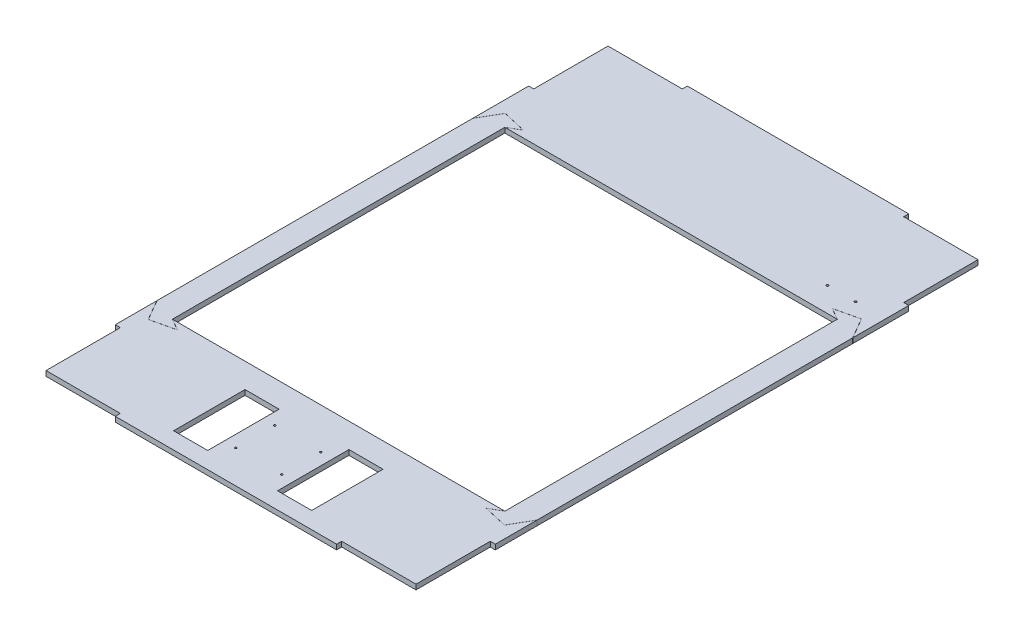
SolidWorks part; units mm, degrees
ref_plane "Front Plane" through (0, 0, 0) normal (0, 0, 1) x (1, 0, 0)
ref_plane "Top Plane" through (0, 0, 0) normal (0, 1, 0) x (1, 0, 0)
ref_plane "Right Plane" through (0, 0, 0) normal (1, 0, 0) x (0, 0, -1)
sketch "Sketch1" plane through (0, 0, 0) normal (0, 1, 0) x (1, 0, 0)
  line L0 (44, -285.5) -> (-44, -285.5) construction
  line L1 (-209.5, -209.5) -> (209.5, -209.5)
  line L2 (-209.5, -209.5) -> (-209.5, 209.5)
  line L3 (-209.5, 209.5) -> (209.5, 209.5)
  line L4 (209.5, -209.5) -> (209.5, 209.5)
  line L5 (-209.5, -209.5) -> (209.5, 209.5) construction
  line L6 (-209.5, 209.5) -> (209.5, -209.5) construction
  line L7 (-239.5, -351.5) -> (239.5, -351.5)
  line L8 (-239.5, -351.5) -> (-239.5, 369.5)
  line L9 (-239.5, 369.5) -> (239.5, 369.5)
  line L10 (239.5, -351.5) -> (239.5, 369.5)
  line L11 (-97, -340.5) -> (97, -340.5) construction
  line L12 (-97, -340.5) -> (-97, -230.5) construction
  line L13 (-97, -230.5) -> (97, -230.5) construction
  line L14 (97, -340.5) -> (97, -230.5) construction
  line L15 (-97, -340.5) -> (97, -230.5) construction
  line L16 (-97, -230.5) -> (97, -340.5) construction
  line L21 (29, -310) -> (-29, -310) construction
  line L22 (29, -310) -> (29, -261) construction
  line L23 (29, -261) -> (-29, -261) construction
  line L24 (-29, -310) -> (-29, -261) construction
  line L25 (29, -310) -> (-29, -261) construction
  line L26 (29, -261) -> (-29, -310) construction
  line L27 (-44, -330.5) -> (-87, -330.5)
  line L28 (-44, -330.5) -> (-44, -240.5)
  line L29 (-44, -240.5) -> (-87, -240.5)
  line L30 (-87, -330.5) -> (-87, -240.5)
  line L31 (87, -330.5) -> (44, -330.5)
  line L32 (87, -330.5) -> (87, -240.5)
  line L33 (87, -240.5) -> (44, -240.5)
  line L34 (44, -330.5) -> (44, -240.5)
  circle A0 centre (-29, -310) radius 1.25
  circle A1 centre (-29, -261) radius 1.25
  circle A2 centre (29, -261) radius 1.25
  circle A3 centre (29, -310) radius 1.25
  point P0 (0, 0)
  point P6 (0, 0)
  point P11 (0, -351.5)
  point P12 (0, -285.5)
  point P17 (0, -285.5)
  point P18 (0, -285.5)
  dimension "D10" = 2.5
  dimension "D1" = 419
  dimension "D2" = 30
  dimension "D3" = 11
  dimension "D4" = 160
  dimension "D5" = 194
  dimension "D6" = 110
  dimension "D7" = 21
  dimension "D8" = 58
  dimension "D9" = 49
  dimension "D11" = 10
  dimension "D12" = 15
  dimension "D13" = 10
extrude "Boss-Extrude1" add sketch "Sketch1" along normal mid plane 6.35
sketch "Sketch2" plane through (0, 3.175, 0) normal (0, 1, 0) x (1, 0, 0)
  line L0 (-239.5, 369.5) -> (-239.5, 269.5)
  line L1 (-239.5, 369.5) -> (-239.5, -351.5) construction
  line L2 (-239.5, 269.5) -> (-233.15, 269.5)
  line L3 (-233.15, 269.5) -> (-233.15, 363.15)
  line L4 (-233.15, 363.15) -> (-139.5, 363.15)
  line L5 (-139.5, 363.15) -> (-139.5, 369.5)
  line L6 (239.5, 369.5) -> (-239.5, 369.5) construction
  line L7 (-139.5, 369.5) -> (-239.5, 369.5)
  line L8 (239.5, 369.5) -> (139.5, 369.5)
  line L9 (139.5, 369.5) -> (139.5, 363.15)
  line L10 (139.5, 363.15) -> (233.15, 363.15)
  line L11 (233.15, 363.15) -> (233.15, 269.5)
  line L12 (233.15, 269.5) -> (239.5, 269.5)
  line L13 (239.5, -351.5) -> (239.5, 369.5) construction
  line L14 (239.5, 269.5) -> (239.5, 369.5)
  line L15 (239.5, -351.5) -> (239.5, -251.5)
  line L16 (239.5, -251.5) -> (233.15, -251.5)
  line L17 (233.15, -251.5) -> (233.15, -345.15)
  line L18 (233.15, -345.15) -> (139.5, -345.15)
  line L19 (139.5, -345.15) -> (139.5, -351.5)
  line L20 (-239.5, -351.5) -> (239.5, -351.5) construction
  line L21 (139.5, -351.5) -> (239.5, -351.5)
  line L22 (-239.5, -351.5) -> (-139.5, -351.5)
  line L23 (-139.5, -351.5) -> (-139.5, -345.15)
  line L24 (-139.5, -345.15) -> (-233.15, -345.15)
  line L25 (-233.15, -345.15) -> (-233.15, -251.5)
  line L26 (-233.15, -251.5) -> (-239.5, -251.5)
  line L27 (-239.5, -251.5) -> (-239.5, -351.5)
  dimension "D1" = 100
  dimension "D2" = 6.35
extrude "Cut-Extrude1" cut sketch "Sketch2" against normal through all
sketch "Sketch3" plane through (0, 3.175, 0) normal (0, 1, 0) x (1, 0, 0)
  line L0 (201.88, 240.12) -> (166.32, 240.12) construction
  line L2 (209.5, 209.5) -> (-209.5, 209.5) construction
  line L3 (161.24, 232.5) -> (209.5, 232.5) construction
  line L4 (161.24, 232.5) -> (161.24, 268.06) construction
  line L5 (161.24, 268.06) -> (209.5, 268.06) construction
  line L6 (209.5, 232.5) -> (209.5, 268.06) construction
  line L7 (209.5, -209.5) -> (209.5, 209.5) construction
  circle A0 centre (166.32, 240.12) radius 1.375
  circle A1 centre (201.88, 240.12) radius 1.375
  dimension "D2" = 2.75
  dimension "D1" = 35.56
  dimension "D3" = 35.56
  dimension "D4" = 48.26
  dimension "D5" = 40.64
  dimension "D6" = 27.94
  dimension "D7" = 23
extrude "Cut-Extrude2" cut sketch "Sketch3" against normal through all
sketch "Sketch4" plane through (0, 3.175, 0) normal (0, 1, 0) x (1, 0, 0)
  line L0 (-209.5, -209.5) -> (-194.7696, -218.0046)
  line L1 (-194.7696, -218.0046) -> (-224.4504, -224.8859)
  line L2 (-224.4504, -224.8859) -> (-239.5, -198.8192)
  line L3 (-239.5, 269.5) -> (-239.5, -251.5) construction
  line L4 (-209.5, -209.5) -> (209.5, -209.5) construction
  line L5 (-239.5, -198.8192) -> (-239.5, -199.0192)
  line L6 (-239.5, -199.0192) -> (-224.5, -225)
  line L7 (-224.5, -225) -> (-194.5, -218.0448)
  line L8 (-194.5, -218.0448) -> (-209.3, -209.5)
  line L9 (-209.3, -209.5) -> (-209.5, -209.5)
  line L10 (-202.1348, -213.7523) -> (-202.0848, -213.6657) construction
  line L11 (-209.61, -221.4452) -> (-209.5874, -221.5427) construction
  line L12 (-231.9752, -211.8525) -> (-232.0618, -211.9025) construction
  line L13 (-3.4925, 0) -> (3.4925, 0) construction
  line L14 (-209.3, 209.5) -> (-209.5, 209.5)
  line L15 (-194.5, 218.0448) -> (-209.3, 209.5)
  line L16 (-224.5, 225) -> (-194.5, 218.0448)
  line L17 (-239.5, 199.0192) -> (-224.5, 225)
  line L18 (-239.5, 198.8192) -> (-239.5, 199.0192)
  line L19 (-224.4504, 224.8859) -> (-239.5, 198.8192)
  line L20 (-194.7696, 218.0046) -> (-224.4504, 224.8859)
  line L21 (-209.5, 209.5) -> (-194.7696, 218.0046)
  line L22 (0, -3.4925) -> (0, 3.4925) construction
  line L23 (194.5, -218.0448) -> (209.3, -209.5)
  line L24 (224.5, -225) -> (194.5, -218.0448)
  line L25 (239.5, -199.0192) -> (224.5, -225)
  line L26 (239.5, -198.8192) -> (239.5, -199.0192)
  line L27 (224.4504, -224.8859) -> (239.5, -198.8192)
  line L28 (194.7696, -218.0046) -> (224.4504, -224.8859)
  line L29 (209.5, -209.5) -> (194.7696, -218.0046)
  line L30 (209.3, -209.5) -> (209.5, -209.5)
  line L31 (194.5, 218.0448) -> (209.3, 209.5)
  line L32 (224.5, 225) -> (194.5, 218.0448)
  line L33 (239.5, 199.0192) -> (224.5, 225)
  line L34 (239.5, 198.8192) -> (239.5, 199.0192)
  line L35 (224.4504, 224.8859) -> (239.5, 198.8192)
  line L36 (194.7696, 218.0046) -> (224.4504, 224.8859)
  line L37 (209.5, 209.5) -> (194.7696, 218.0046)
  line L38 (209.3, 209.5) -> (209.5, 209.5)
  dimension "D1" = 30
  dimension "D2" = 30
  dimension "D3" = 0.1
  dimension "D4" = 450
  dimension "D5" = 15
  dimension "D6" = 15
extrude "Cut-Extrude3" cut sketch "Sketch4" against normal through all
